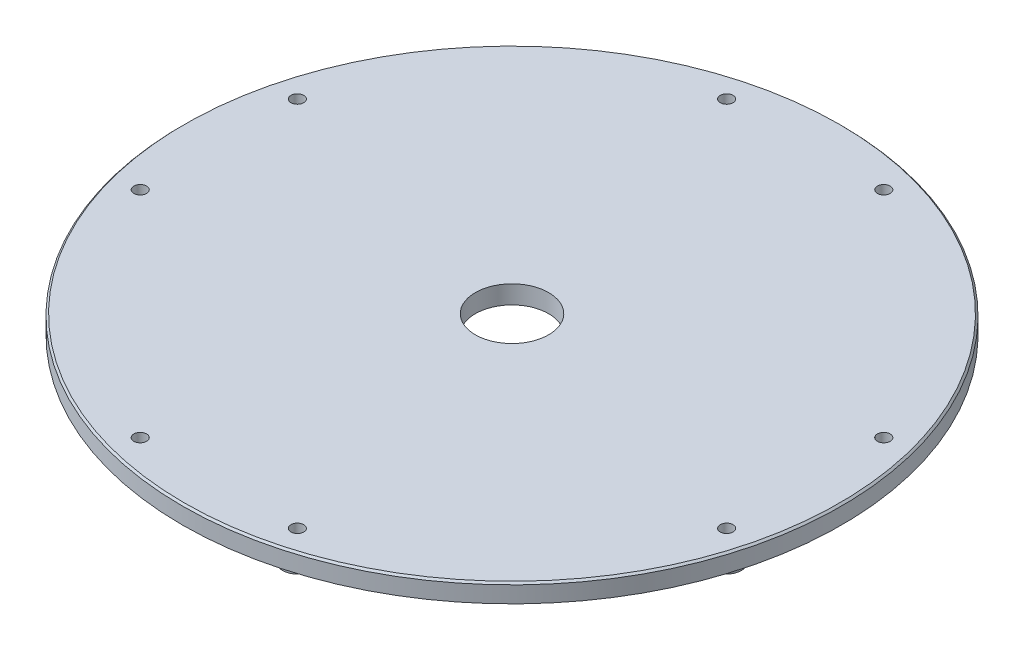
SolidWorks part; units mm, degrees
ref_plane "Ebene vorne" through (0, 0, 0) normal (0, 0, 1) x (1, 0, 0)
ref_plane "Ebene oben" through (0, 0, 0) normal (0, 1, 0) x (1, 0, 0)
ref_plane "Ebene rechts" through (0, 0, 0) normal (1, 0, 0) x (0, 0, -1)
sketch "Skizze1" plane through (0, 0, 0) normal (0, 1, 0) x (1, 0, 0)
  circle A0 centre (0, 0) radius 90
  dimension "D1" = 180
extrude "Aufsatz-Linear austragen1" add sketch "Skizze1" along normal blind 5
sketch "Skizze2" plane through (0, 0, 0) normal (0, -1, 0) x (1, 0, 0)
  line L0 (0, 0) -> (0, 90) construction
  line L1 (15, 30) -> (15, 88.7412) construction
  line L2 (-15, 30) -> (-15, 88.7412) construction
  line L3 (-15, 30) -> (-15, 40)
  line L4 (-15, 30) -> (-21, 30)
  line L5 (-15, 40) -> (-21, 40)
  line L6 (-21, 30) -> (-21, 40)
  line L7 (15, 30) -> (15, 40)
  line L8 (15, 30) -> (21, 30)
  line L9 (15, 40) -> (21, 40)
  line L10 (21, 30) -> (21, 40)
  circle A0 centre (0, 0) radius 90 construction
  dimension "D1" = 15
  dimension "D2" = 60
  dimension "D3" = 10
  dimension "D4" = 6
extrude "Aufsatz-Linear austragen2" add sketch "Skizze2" along normal blind 14
chamfer "Fase1" distance 14 angle 45 2 edges at (18, 0, 40) (-18, 0, 40)
sketch "Skizze3" plane through (21, 0, 0) normal (1, 0, 0) x (0, 0, -1)
  line L0 (-40, -14) -> (-40, 0) construction
  line L2 (-40, 0) -> (-30, -14) construction
  line L3 (-90, 0) -> (90, 0) construction
  circle A0 centre (-35, -7) radius 2.15
  dimension "D1" = 4.3
extrude "Schnitt-Linear austragen1" cut sketch "Skizze3" against normal blind 42
pattern_circular "Kreismuster1" count 3 over 360 about axis through (0, 5, 0) along (0, -1, 0) of "Aufsatz-Linear austragen2", "Fase1", "Schnitt-Linear austragen1"
sketch "Skizze4" plane through (0, 0, 0) normal (0, -1, 0) x (1, 0, 0)
  line L0 (-15, 54) -> (-15, 78.5812)
  line L1 (15, 54) -> (15, 78.5812)
  line L2 (54.2654, -14.0096) -> (75.5533, -26.3002)
  line L3 (39.2654, -39.9904) -> (60.5533, -52.281)
  line L4 (-39.2654, -39.9904) -> (-60.5533, -52.281)
  line L5 (-54.2654, -14.0096) -> (-75.5533, -26.3002)
  circle A0 centre (0, 0) radius 33.541
  circle A1 centre (0, 0) radius 80
  circle A2 centre (0, 0) radius 90 construction
  circle A3 centre (0, 0) radius 74
  circle A4 centre (0, 0) radius 36.6197
  point P28 (0, 0)
  line M6 (33.4808, -2.0096) -> (36.4808, 3.1865)
  line M10 (-18.4808, -27.9904) -> (-15.4808, -33.1865)
  line M14 (-15, 30) -> (-21, 30)
  line M19 (21, 30) -> (15, 30)
  line M23 (-36.4808, 3.1865) -> (-33.4808, -2.0096)
  line M27 (15.4808, -33.1865) -> (18.4808, -27.9904)
  dimension "D1" = 10
  dimension "D2" = 6
  dimension "D3" = 3
extrude "Aufsatz-Linear austragen3" add sketch "Skizze4" along normal blind 3 contours A3 L0 A1 L5 | A3 L2 A1 L1 | A3 L4 A1 L3 | A4 A0 M10 M27 | A4 A0 M14 M23 | A4 A0 M6 M19 region at (-65.1545, 0, 37.617) region at (16.2339, 0, 75.5225) region at (0, 0, -75.2496) region at (29.0481, 0, 16.7709) region at (-29.0481, 0, 16.7709) region at (0, 0, -33.5418)
sketch "Skizze6" plane through (0, 0, 0) normal (0, -1, 0) x (1, 0, 0)
  line L0 (0, 0) -> (0, -90) construction
  line L1 (0, 0) -> (-20.7055, -77.2741) construction
  line L2 (-13.2849, -34.125) -> (-27.1344, -85.8121) construction
  line L3 (-5.5575, -36.1955) -> (-19.407, -87.8827) construction
  line L4 (-3.8637, 1.0353) -> (-27.1574, -85.898) construction
  line L5 (3.8637, -1.0353) -> (-19.43, -87.9686) construction
  line L6 (-24.5433, -76.1421) -> (-25.3198, -79.0399)
  line L7 (-16.8159, -78.2127) -> (-17.5924, -81.1105)
  line L8 (-17.5924, -81.1105) -> (-25.3198, -79.0399) construction
  line L9 (0, 0) -> (-23.2937, -86.9333) construction
  line L10 (-24.5433, -76.1421) -> (-16.8159, -78.2127)
  line L11 (17.5924, -81.1105) -> (25.3198, -79.0399) construction
  line L12 (0, 0) -> (20.7055, -77.2741) construction
  line L13 (5.5575, -36.1955) -> (19.407, -87.8827) construction
  line L14 (13.2849, -34.125) -> (27.1344, -85.8121) construction
  line L15 (24.5433, -76.1421) -> (16.8159, -78.2127)
  line L16 (16.8159, -78.2127) -> (17.5924, -81.1105)
  line L17 (24.5433, -76.1421) -> (25.3198, -79.0399)
  circle A0 centre (0, 0) radius 90 construction
  arc A1 (-15.4808, -33.1865) -> (15.4808, -33.1865) centre (0, 0) ccw construction
  arc A4 (-60.5533, -52.281) -> (60.5533, -52.281) centre (0, 0) ccw construction
  arc A5 (-17.5924, -81.1105) -> (-25.3198, -79.0399) centre (-21.4561, -80.0752) cw
  arc A6 (17.5924, -81.1105) -> (25.3198, -79.0399) centre (21.4561, -80.0752) ccw
  dimension "D1" = 15
  dimension "D4" = 3
  dimension "D2" = 4
  dimension "D3" = 4
extrude "Aufsatz-Linear austragen4" add sketch "Skizze6" along normal up to surface (3 mm away) up to face at (0, -3, -63.8758)
sketch "Skizze7" plane through (0, -3, 0) normal (0, -1, 0) x (1, 0, 0)
  line L0 (-25.3198, -79.0399) -> (-17.5924, -81.1105) construction
  line L1 (17.5924, -81.1105) -> (25.3198, -79.0399) construction
  line L2 (25.3198, -79.0399) -> (24.5433, -76.1421) construction
  circle A0 centre (-21.4561, -80.0752) radius 1.75
  circle A1 centre (21.4561, -80.0752) radius 1.75
  arc A2 (17.5924, -81.1105) -> (25.3198, -79.0399) centre (21.4561, -80.0752) ccw construction
  dimension "D1" = 3.5
extrude "Schnitt-Linear austragen2" cut sketch "Skizze7" against normal up to next
pattern_circular "Kreismuster2" count 4 over 360 about axis through (0, -3, 0) along (0, 1, 0) of "Aufsatz-Linear austragen4", "Schnitt-Linear austragen2"
sketch "Skizze8" plane through (0, 5, 0) normal (0, 1, 0) x (1, 0, 0)
  circle A0 centre (0, 0) radius 10
  dimension "D1" = 20
extrude "Schnitt-Linear austragen3" cut sketch "Skizze8" against normal up to next
chamfer "Fase2" distance 0.5 angle 45 1 edges at (0, 5, 90)
